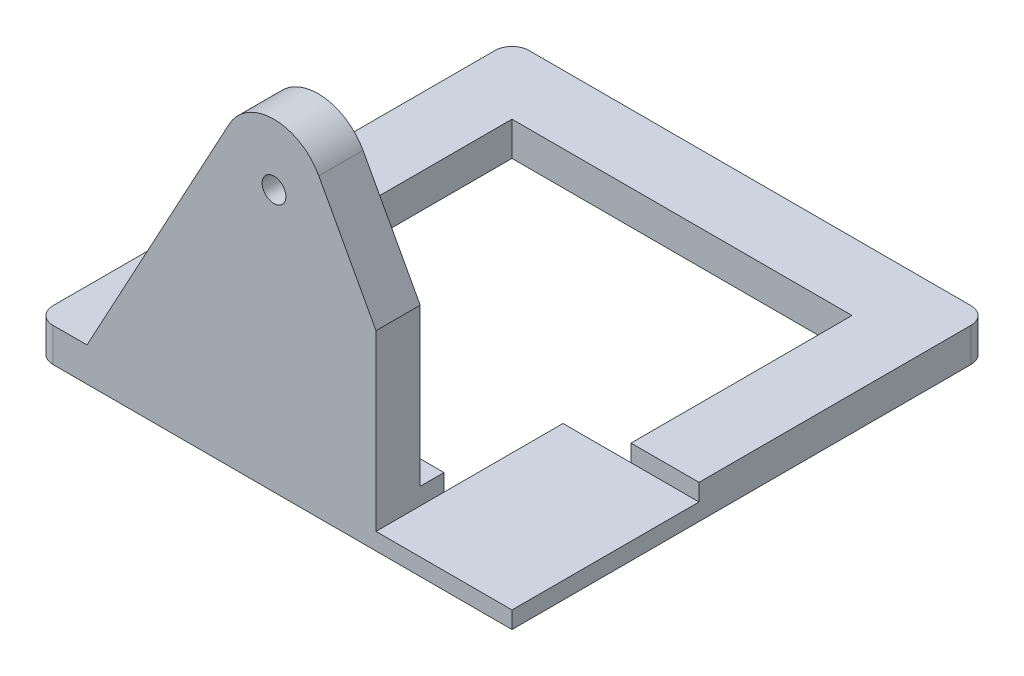
SolidWorks part; units mm, degrees
material "ABS PC"
ref_plane "Front Plane" through (0, 0, 0) normal (0, 0, 1) x (1, 0, 0)
ref_plane "Top Plane" through (0, 0, 0) normal (0, 1, 0) x (1, 0, 0)
ref_plane "Right Plane" through (0, 0, 0) normal (1, 0, 0) x (0, 0, -1)
sketch "Sketch1" plane through (0, 0, 0) normal (0, 1, 0) x (1, 0, 0)
  line L1 (-70, -70) -> (70, -70)
  line L2 (-70, -70) -> (-70, 70)
  line L3 (-70, 70) -> (70, 70)
  line L4 (70, -70) -> (70, 70)
  line L5 (-70, -70) -> (70, 70) construction
  line L6 (-70, 70) -> (70, -70) construction
  line L7 (-50, -50) -> (50, -50)
  line L8 (-50, -50) -> (-50, 50)
  line L9 (-50, 50) -> (50, 50)
  line L10 (50, -50) -> (50, 50)
  line L11 (-50, -50) -> (50, 50) construction
  line L12 (-50, 50) -> (50, -50) construction
  point P0 (0, 0)
  point P6 (0, 0)
  dimension "D1" = 140
  dimension "D2" = 100
extrude "Boss-Extrude1" add sketch "Sketch1" along normal blind 10
ref_plane "Plane1" through (0, 0, 60) normal (0, 0, -1) x (-1, 0, 0)
sketch "Sketch2" plane through (0, 0, 60) normal (0, 0, -1) x (-1, 0, 0)
  line L0 (70, 10) -> (-70, 10) construction
  line L1 (55, 10) -> (-55, 10)
  line L2 (55, 10) -> (13.1876, 87.1474)
  line L3 (-55, 10) -> (-13.1876, 87.1474)
  arc A0 (-13.1876, 87.1474) -> (13.1876, 87.1474) centre (0, 80) cw
  dimension "D1" = 70
  dimension "D3" = 15
  dimension "D2" = 55
extrude "Boss-Extrude2" add sketch "Sketch2" along normal blind 3 and the other way up to surface (10 mm away) other way up to face at (0, 5, 70)
sketch "Sketch4" plane through (0, 0, 57) normal (0, 0, -1) x (-1, 0, 0)
  circle A0 centre (0, 77) radius 8.55
  arc A3 (13.1876, 87.1474) -> (-13.1876, 87.1474) centre (0, 80) ccw construction
  point P6 (0, 95)
  dimension "D1" = 17.1
  dimension "D2" = 18
extrude "Cut-Extrude2" cut sketch "Sketch4" against normal blind 6
sketch "Sketch5" plane through (0, 0, 63) normal (0, 0, -1) x (-1, 0, 0)
  circle A0 centre (0, 77) radius 3.5
  dimension "D1" = 7
extrude "Cut-Extrude3" cut sketch "Sketch5" against normal through all
fillet "Fillet1" radius 5 4 edges at (70, 5, -70) (70, 5, 70) (-70, 5, 70) (-70, 5, -70)
sketch "Sketch6" plane through (0, 0, 0) normal (0, 1, 0) x (1, 0, 0)
  line L0 (55, -70) -> (13.1876, -70) construction
  line L1 (30, -70) -> (70, -70)
  line L2 (30, -70) -> (30, -15)
  line L3 (30, -15) -> (70, -15)
  line L4 (70, -70) -> (70, -15)
  line L5 (70, -65) -> (70, 65) construction
  dimension "D1" = 40
  dimension "D2" = 55
extrude "Cut-Extrude4" cut sketch "Sketch6" along normal through all from offset 5
extrude "Boss-Extrude4" add sketch "Sketch6<3>" along normal up to surface (5 mm away) up to face at (52.2908, 5, 48.0051)
sketch "Sketch6<3>" plane through (0, 0, 0) normal (0, 1, 0) x (1, 0, 0) same geometry as "Sketch6"
